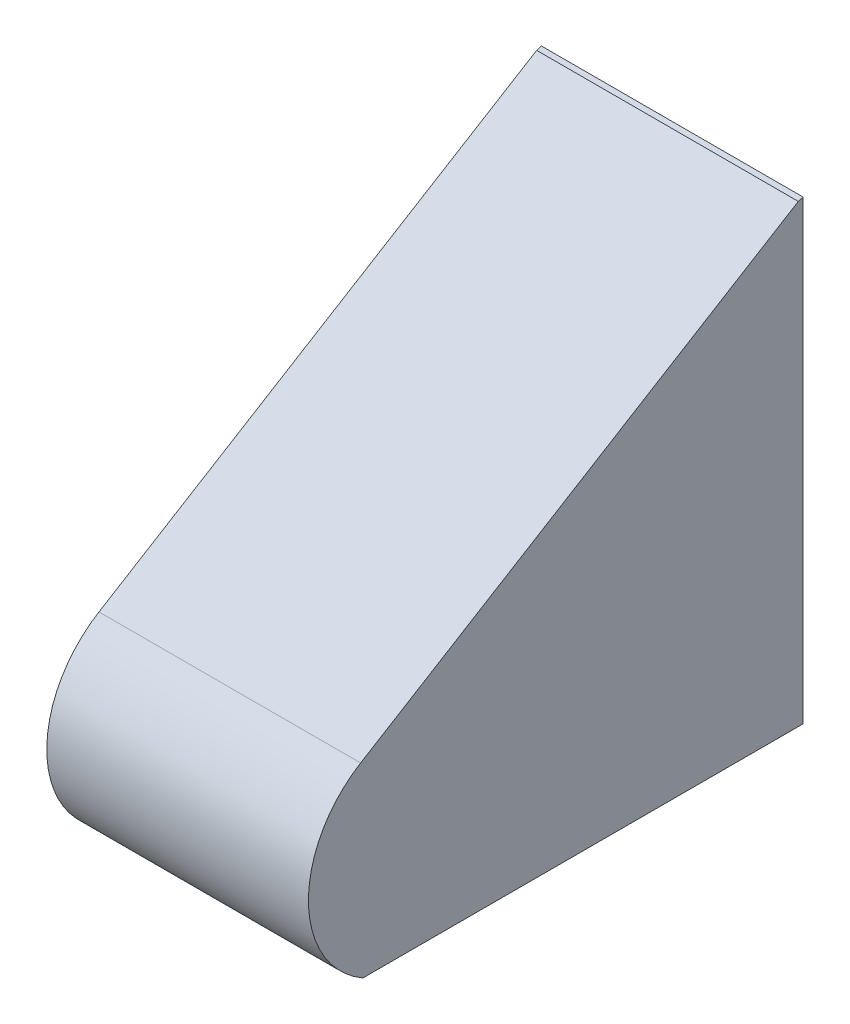
SolidWorks part; units mm, degrees
material "ABS"
ref_plane "Front Plane" through (0, 0, 0) normal (0, 0, 1) x (1, 0, 0)
ref_plane "Top Plane" through (0, 0, 0) normal (0, 1, 0) x (1, 0, 0)
ref_plane "Right Plane" through (0, 0, 0) normal (1, 0, 0) x (0, 0, -1)
sketch "Sketch1" plane through (0, 0, 0) normal (1, 0, 0) x (0, 0, -1)
  line L0 (0, -114.3) -> (0, 114.3) construction
  line L1 (0, 75.1586) -> (0, -75.1586) construction
  line L2 (75.1586, 0) -> (-75.1586, 0) construction
  line L3 (0, 0) -> (-228.6, 0) construction
  line L4 (0, -114.3) -> (-228.6, -114.3)
  line L5 (-228.6, -114.3) -> (-228.6, -25.4) construction
  line L6 (-228.6, -25.4) -> (0, 114.3)
  line L11 (0, 114.3) -> (0, 119.126)
  line L13 (0, -119.126) -> (-229.9255, -119.126)
  line L14 (-231.1165, -21.2821) -> (-2.5165, 118.4179)
  line L15 (0, -119.126) -> (0, -114.3)
  line L16 (-2.5165, 118.4179) -> (0, 119.126)
  arc A0 (-228.6, -25.4) -> (-228.6, -114.3) centre (-201.4361, -69.85) ccw
  arc A1 (-231.1165, -21.2821) -> (-229.9255, -119.126) centre (-201.4361, -69.85) ccw
  dimension "D1" = 114.3
  dimension "D2" = 114.3
  dimension "D3" = 228.6
  dimension "D4" = 88.9
  dimension "D6" = 4.826
  dimension "D5" = 4.826
extrude "Boss-Extrude1" add sketch "Sketch1" along normal blind 63.5 and the other way blind 63.5
sketch "Sketch2" plane through (63.5, 0, 0) normal (1, 0, 0) x (0, 0, -1)
  line L9 (-229.9255, -119.126) -> (0, -119.126) construction
  line L10 (-2.5165, 118.4179) -> (-231.1165, -21.2821) construction
  line L11 (-229.9255, -119.126) -> (0, -119.126)
  line L12 (-2.5165, 118.4179) -> (-231.1165, -21.2821)
  line L13 (0, 119.126) -> (-2.5165, 118.4179) construction
  line L14 (0, 119.126) -> (-2.5165, 118.4179)
  line L15 (0, 119.126) -> (0, -119.126)
  arc A1 (-231.1165, -21.2821) -> (-229.9255, -119.126) centre (-201.4361, -69.85) ccw construction
  arc A2 (-231.1165, -21.2821) -> (-229.9255, -119.126) centre (-201.4361, -69.85) ccw
extrude "Boss-Extrude2" add sketch "Sketch2" along normal blind 4.826
mirror "Mirror1" about plane through (0, 0, 0) normal (1, 0, 0) of "Boss-Extrude2"
